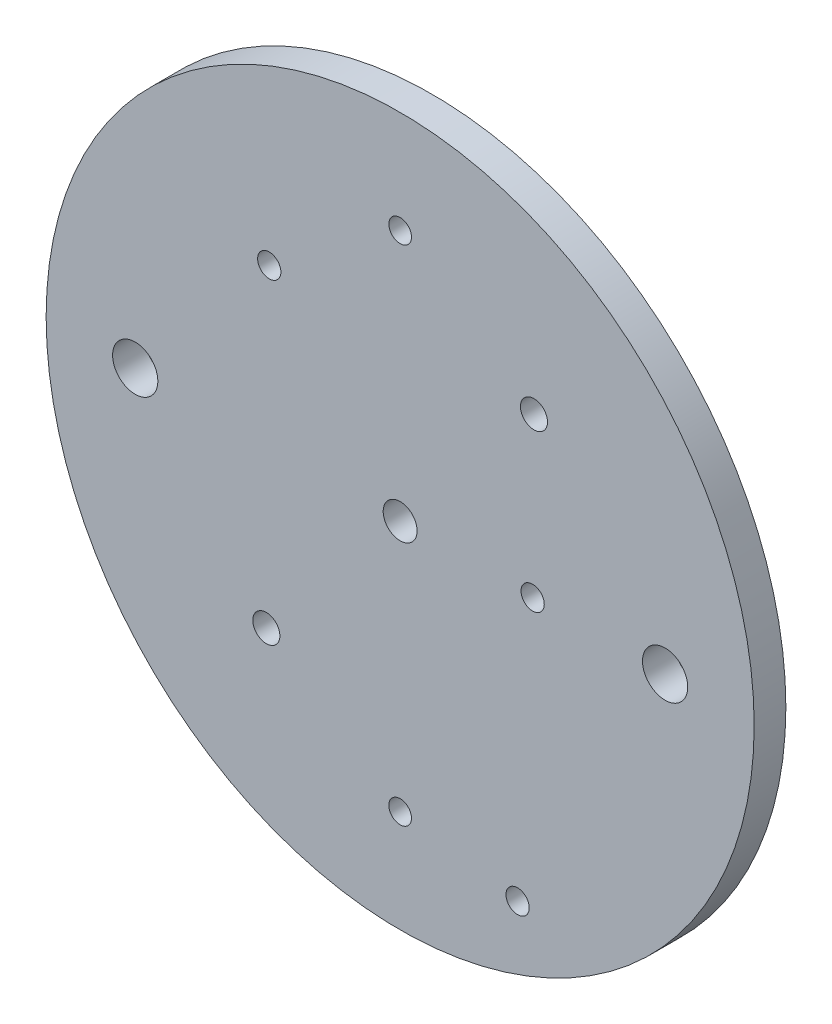
SolidWorks part; units mm, degrees
material "E-Glass Fiber"
ref_plane "Front Plane" through (0, 0, 0) normal (0, 0, 1) x (1, 0, 0)
ref_plane "Top Plane" through (0, 0, 0) normal (0, 1, 0) x (1, 0, 0)
ref_plane "Right Plane" through (0, 0, 0) normal (1, 0, 0) x (0, 0, -1)
sketch "Sketch1" plane through (0, 0, 0) normal (0, 0, 1) x (1, 0, 0)
  circle A0 centre (0, 0) radius 49.6697
  dimension "D1" = 99.3394
extrude "Boss-Extrude1" add sketch "Sketch1" along normal blind 4.445
sketch "Sketch2" plane through (0, 0, 4.445) normal (0, 0, 1) x (1, 0, 0)
  line L0 (37.1729, 0) -> (0, 0) construction
  line L1 (0, 0) -> (-37.1729, 0) construction
  line L2 (0, 0) -> (0, 35.306) construction
  line L3 (0, 0) -> (18.7758, 22.3762) construction
  line L4 (0, 0) -> (-18.3677, 21.8897) construction
  line L5 (16.4781, -37.9415) -> (18.5865, 0) construction
  circle A0 centre (0, 0) radius 2.3812
  circle A1 centre (37.1729, 0) radius 3.175
  circle A2 centre (-37.1729, 0) radius 3.175
  dimension "D1" = 4.7625
  dimension "D2" = 6.35
  dimension "D3" = 74.3458
  dimension "D5" = 29.21
  dimension "D6" = 50
  dimension "D4" = 35.306
  dimension "D7" = 28.575
  dimension "D8" = 50
  dimension "D9" = 38
extrude "Cut-Extrude1" cut sketch "Sketch2" against normal through all
hole_wizard "#4 Clearance Hole1" positions "Sketch4" profile "Sketch3" hole size "#4" standard "ANSI Inch" end condition through all
sketch "Sketch4" plane through (0, 0, 4.445) normal (0, 0, 1) x (1, 0, 0)
  point P0 (-18.3677, 21.8897)
  point P4 (18.5865, 0)
  point P7 (16.4781, -37.9415)
sketch "Sketch3" plane through (-18.3677, 21.8897, 4.445) normal (1, 0, 0) x (0, -1, 0)
  line L0 (0, 0) -> (0, 4.445)
  line L1 (0, 4.445) -> (1.6319, 4.445)
  line L2 (1.6319, 4.445) -> (1.6319, 0)
  line L5 (1.6319, 0) -> (0, 0)
  line L11 (0, -6.35) -> (0, 107.95) construction
  dimension "Thru Hole Dia." = 3.2639
  dimension "Thru Hole Depth" = 4.445
hole_wizard "#6 Clearance Hole1" positions "Sketch6" profile "Sketch7" hole size "#6" standard "ANSI Inch" end condition through all
sketch "Sketch6" plane through (0, 0, 4.445) normal (0, 0, 1) x (1, 0, 0)
  point P0 (18.7758, 22.3762)
sketch "Sketch7" plane through (18.7758, 22.3762, 4.445) normal (1, 0, 0) x (0, -1, 0)
  line L0 (0, 0) -> (0, 4.445)
  line L1 (0, 4.445) -> (1.8986, 4.445)
  line L2 (1.8986, 4.445) -> (1.8986, 0)
  line L5 (1.8986, 0) -> (0, 0)
  line L11 (0, -6.35) -> (0, 107.95) construction
  dimension "Thru Hole Dia." = 3.7973
  dimension "Thru Hole Depth" = 4.445
hole_wizard "1/8 (0.125) Diameter Hole1" positions "Sketch9" profile "Sketch10" hole size "1/8" standard "ANSI Inch" end condition through all
sketch "Sketch9" plane through (0, 0, 4.445) normal (0, 0, 1) x (1, 0, 0)
  point P0 (0, 35.306)
sketch "Sketch10" plane through (0, 35.306, 4.445) normal (1, 0, 0) x (0, -1, 0)
  line L0 (0, 0) -> (0, 4.445)
  line L1 (0, 4.445) -> (1.5875, 4.445)
  line L2 (1.5875, 4.445) -> (1.5875, 0)
  line L5 (1.5875, 0) -> (0, 0)
  line L11 (0, -6.35) -> (0, 107.95) construction
  dimension "Thru Hole Dia." = 3.175
  dimension "Thru Hole Depth" = 4.445
pattern_circular "CirPattern1" count 2 over 180 about axis through (0, 0, 0) along (0, 0, 1) of "#6 Clearance Hole1", "1/8 (0.125) Diameter Hole1"
